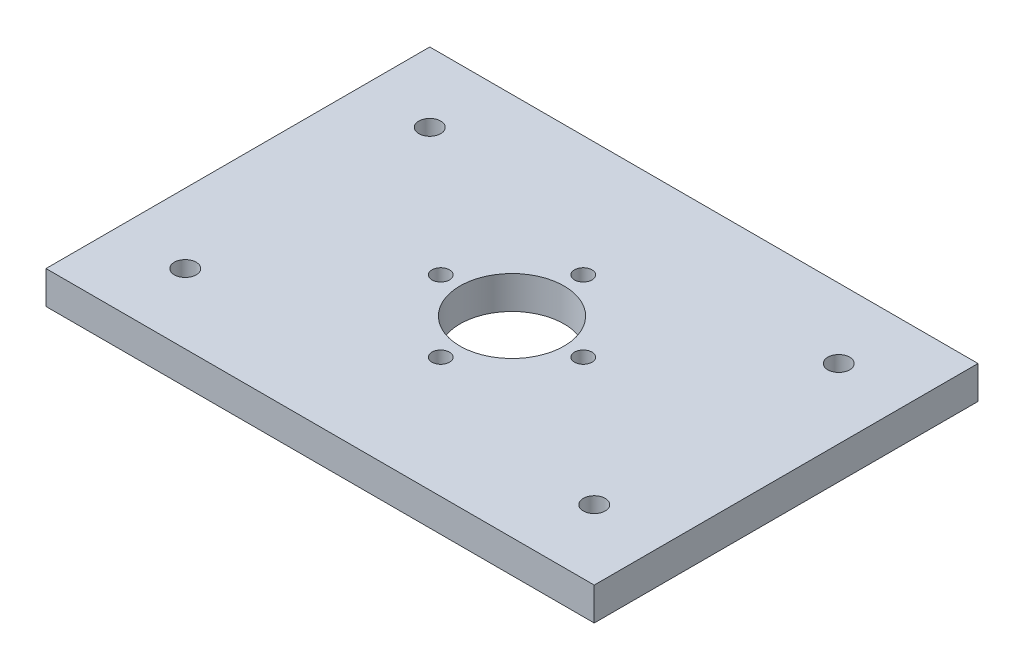
SolidWorks part; units mm, degrees
ref_plane "Front Plane" through (0, 0, 0) normal (0, 0, 1) x (1, 0, 0)
ref_plane "Top Plane" through (0, 0, 0) normal (0, 1, 0) x (1, 0, 0)
ref_plane "Right Plane" through (0, 0, 0) normal (1, 0, 0) x (0, 0, -1)
sketch "Sketch1" plane through (0, 0, 0) normal (0, 1, 0) x (1, 0, 0)
  line L0 (0, -55) -> (0, 55) construction
  line L1 (-50, 35) -> (50, 35)
  line L2 (-50, 35) -> (-50, -35)
  line L3 (-50, -35) -> (50, -35)
  line L4 (50, 35) -> (50, -35)
  line L5 (-50, 35) -> (50, -35) construction
  line L6 (-50, -35) -> (50, 35) construction
  line L7 (-55, 0) -> (55, 0) construction
  line L9 (-37.3, -22.3) -> (37.3, -22.3) construction
  line L10 (-37.3, -22.3) -> (-37.3, 22.3) construction
  line L11 (-37.3, 22.3) -> (37.3, 22.3) construction
  line L12 (37.3, -22.3) -> (37.3, 22.3) construction
  line L13 (-37.3, -22.3) -> (37.3, 22.3) construction
  line L14 (-37.3, 22.3) -> (37.3, -22.3) construction
  circle A0 centre (0, 0) radius 13 construction
  circle A1 centre (0, 13) radius 1.5 construction
  circle A2 centre (13, 0) radius 1.5 construction
  circle A3 centre (0, -13) radius 1.5 construction
  circle A4 centre (-13, 0) radius 1.5 construction
  circle A7 centre (0, 0) radius 9.5
  circle A8 centre (-17.5, 25) radius 2.5 construction
  circle A9 centre (17.5, 25) radius 2.5 construction
  circle A10 centre (17.5, -25) radius 2.5 construction
  circle A11 centre (-17.5, -25) radius 2.5 construction
  circle A12 centre (-50, 25) radius 2.5 construction
  circle A13 centre (-50, -25) radius 2.5 construction
  circle A14 centre (50, -25) radius 2.5 construction
  circle A15 centre (50, 25) radius 2.5 construction
  circle A18 centre (-37.3, 22.3) radius 2
  circle A19 centre (37.3, 22.3) radius 2
  circle A20 centre (37.3, -22.3) radius 2
  circle A21 centre (-37.3, -22.3) radius 2
  dimension "D1" = 26
  dimension "D2" = 3
  dimension "D4" = 19
  dimension "D7" = 5
  dimension "D10" = 5
  dimension "D13" = 12.7
  dimension "D15" = 4
  dimension "D5" = 17.5
  dimension "D6" = 100
  dimension "D8" = 70
  dimension "D9" = 25
  dimension "D11" = 50
  dimension "D12" = 25
  dimension "D14" = 12.7
  dimension "D3" = 4
extrude "Boss-Extrude1" add sketch "Sketch1" along normal blind 6
hole_wizard "CSK for M3 Flat Head Machine Screw1" positions "Sketch7" profile "Sketch8" countersink size "M3" standard "ANSI Metric" end condition through all
sketch "Sketch7" plane through (0, 0, 0) normal (0, -1, 0) x (-1, 0, 0)
  point P0 (-13, 0)
  point P3 (0, -13)
  point P6 (13, 0)
  point P9 (0, 13)
sketch "Sketch8" plane through (13, 0, 0) normal (1, 0, 0) x (0, 0, -1)
  line L0 (0, 0) -> (0, 6)
  line L1 (0, 6) -> (1.6, 6)
  line L2 (1.6, 6) -> (1.6, 1.55)
  line L3 (1.6, 1.55) -> (3.15, 0)
  line L5 (3.15, 0) -> (0, 0)
  line L6 (-1.6, 1.55) -> (-3.15, 0) construction
  line L11 (0, -6.35) -> (0, 107.95) construction
  dimension "Thru Hole Dia." = 3.2
  dimension "Thru Hole Depth" = 6
  dimension "Near C'Sink Dia." = 6.3
  dimension "Near C'Sink Angle" = 90
sketch "Sketch9" plane through (0, 0, 0) normal (0, 1, 0) x (1, 0, 0)
  line L0 (0, -55) -> (0, 55) construction
  line L1 (-55, 0) -> (55, 0) construction
  circle A0 centre (17.5, 25) radius 6
  circle A1 centre (-17.5, 25) radius 6
  circle A2 centre (-17.5, -25) radius 6
  circle A3 centre (17.5, -25) radius 6
  dimension "D1" = 12
equation "\"testbed_height\" = 91.50mm"
equation "\"plate_thickness\" = 6mm"
equation "\"main_body_splay_length\" = 48.5mm"
equation "\"splay_shaft_length_no_wires\" = 10mm"
equation "\"splay_shaft_length_wires\" = 6.5mm"
equation "\"timing_pulley_offset\" = 0mm"
equation "\"effective_motor_length\" = \"timing_pulley_offset\" + \"splay_shaft_length_no_wires\" + \"main_body_splay_length\""
equation "\"80_20_side\" = 25.4mm"
equation "\"80_20_length\" = 152.4mm"
equation "\"80_20_optic_mount_length\" = \"80_20_length\" - 25.4mm"
equation "\"optic_board_hole_size\" = 6.35mm"
equation "\"total_mounting_length\" = \"testbed_height\" - \"effective_motor_length\" - \"80_20_side\""
equation "\"mounting_vertical_portion_height\" = \"total_mounting_length\" - 2 * \"plate_thickness\""
equation "\"face_mount_width\" = 15.25mm"
equation "\"center_dist_to_face_mount_vertical_screws\" = 5mm"
equation "\"D1@Boss-Extrude1\"=\"plate_thickness\""
